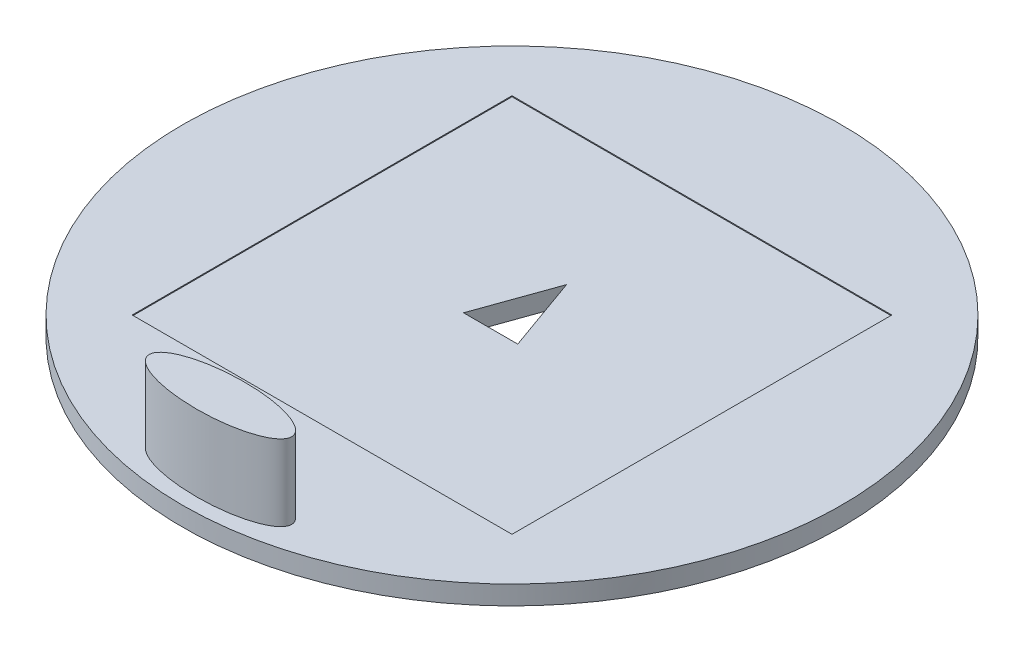
SolidWorks part; units mm, degrees
ref_plane "Front Plane" through (0, 0, 0) normal (0, 0, 1) x (1, 0, 0)
ref_plane "Top Plane" through (0, 0, 0) normal (0, 1, 0) x (1, 0, 0)
ref_plane "Right Plane" through (0, 0, 0) normal (1, 0, 0) x (0, 0, -1)
sketch "Sketch1" plane through (0, 0, 0) normal (0, 1, 0) x (1, 0, 0)
  line L0 (-2.5, -2) -> (2.5, -2) construction
  line L1 (2.5, -2) -> (0, 5) construction
  line L2 (0, 5) -> (-2.5, -2) construction
  line L3 (0, 0) -> (0, -2) construction
  line L4 (0, 5.7433) -> (-2.8548, -2.25)
  line L5 (-2.8548, -2.25) -> (2.8548, -2.25)
  line L6 (2.8548, -2.25) -> (0, 5.7433)
  line L7 (-33.0599, 10.5419) -> (-33.0599, -10.5419)
  circle A0 centre (0, 0) radius 35 construction
  circle A1 centre (0, 0) radius 34.7
  dimension "D1" = 70
  dimension "D3" = 7
  dimension "D4" = 5
  dimension "D5" = 2
  dimension "D2" = 0.3
  dimension "D6" = 0.25
extrude "Boss-Extrude1" add sketch "Sketch1" along normal blind 2 contours L5 L6 L4 | A1 L6 L5 L4 | L7 A1 region at (0, 0, -0.4144) region at (5.1853, 0, -33.3291) region at (-33.7173, 0, 0)
extrude "Cut-Extrude1" cut sketch "Sketch1<4>" along normal blind 4 contours L5 L6 L4 region at (0, 0, -0.4144)
sketch "Sketch1<4>" plane through (0, 0, 0) normal (0, 1, 0) x (1, 0, 0) same geometry as "Sketch1"
sketch "Sketch3" plane through (0, 2, 0) normal (0, 1, 0) x (1, 0, 0)
  line L0 (-7.5, -30.6947) -> (7.5, -30.6947) construction
  ellipse E0 centre (0, -30.6947) end of major axis (7.5, -30.6947) minor radius 2.5
  dimension "D1" = 5
  dimension "D2" = 15
extrude "Boss-Extrude2" add sketch "Sketch3" along normal blind 8
sketch "Sketch4" plane through (0, 2, 0) normal (0, 1, 0) x (1, 0, 0)
  line L1 (-20, 20) -> (20, 20)
  line L2 (-20, 20) -> (-20, -20)
  line L3 (-20, -20) -> (20, -20)
  line L4 (20, 20) -> (20, -20)
  line L5 (-20, 20) -> (20, -20) construction
  line L6 (-20, -20) -> (20, 20) construction
  point P0 (0, 0)
  dimension "D1" = 40
extrude "Cut-Extrude3" cut sketch "Sketch4" against normal blind 0.1
sketch "Sketch7" plane through (0, 0, 0) normal (0, 0, 1) x (1, 0, 0)
  line L0 (-34.7, 1) -> (-29.75, 0)
  line L1 (-34.7, 2) -> (-34.7, 0) construction
  line L2 (-34.7, 0) -> (34.7, 0) construction
  line L3 (-29.75, 0) -> (-34.7, 0)
  line L4 (-34.7, 0) -> (-34.7, 1)
extrude "Cut-Extrude4" cut sketch "Sketch7" against normal blind 21 and the other way blind 22 contours L3 L4 L0
